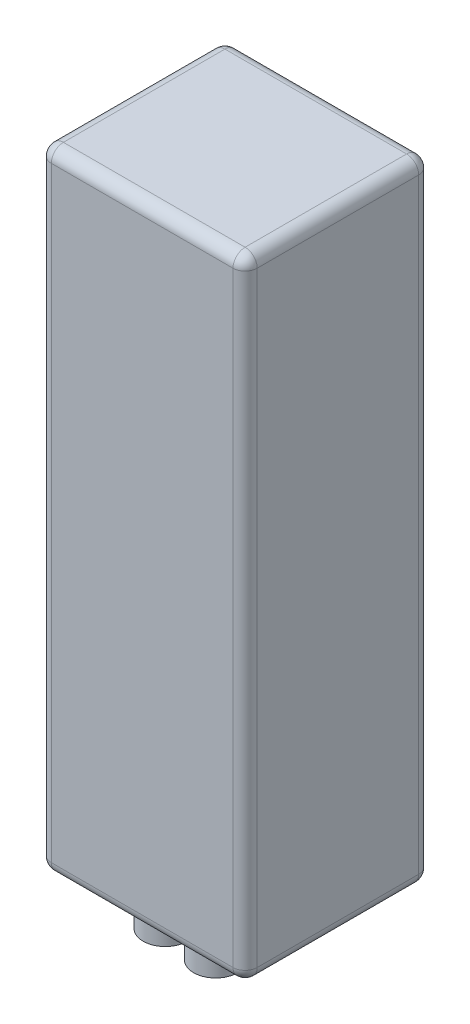
SolidWorks part; units mm, degrees
ref_plane "Front Plane" through (0, 0, 0) normal (0, 0, 1) x (1, 0, 0)
ref_plane "Top Plane" through (0, 0, 0) normal (0, 1, 0) x (1, 0, 0)
ref_plane "Right Plane" through (0, 0, 0) normal (1, 0, 0) x (0, 0, -1)
sketch "Sketch1" plane through (0, 0, 0) normal (0, 1, 0) x (1, 0, 0)
  line L1 (-39.4956, 20.7) -> (11.5044, 20.7)
  line L2 (-39.4956, 20.7) -> (-39.4956, -25.3)
  line L3 (-39.4956, -25.3) -> (11.5044, -25.3)
  line L4 (11.5044, 20.7) -> (11.5044, -25.3)
  dimension "D1" = 46
  dimension "D2" = 51
extrude "Boss-Extrude1" add sketch "Sketch1" along normal blind 156
fillet "Fillet1" radius 3 12 edges at (11.5044, 0, 2.3) (11.5044, 156, 2.3) (-39.4956, 156, 2.3) (-39.4956, 0, 2.3) (11.5044, 78, -20.7) (-13.9956, 156, -20.7) (-39.4956, 78, -20.7) (-13.9956, 0, -20.7) (-39.4956, 78, 25.3) (-13.9956, 156, 25.3) (11.5044, 78, 25.3) (-13.9956, 0, 25.3)
sketch "Sketch2" plane through (0, 0, 0) normal (0, -1, 0) x (1, 0, 0)
  circle A0 centre (-21.2412, 12.3253) radius 5.4797
  circle A1 centre (-8.249, 12.825) radius 5.4797
extrude "Boss-Extrude2" add sketch "Sketch2" along normal blind 10
